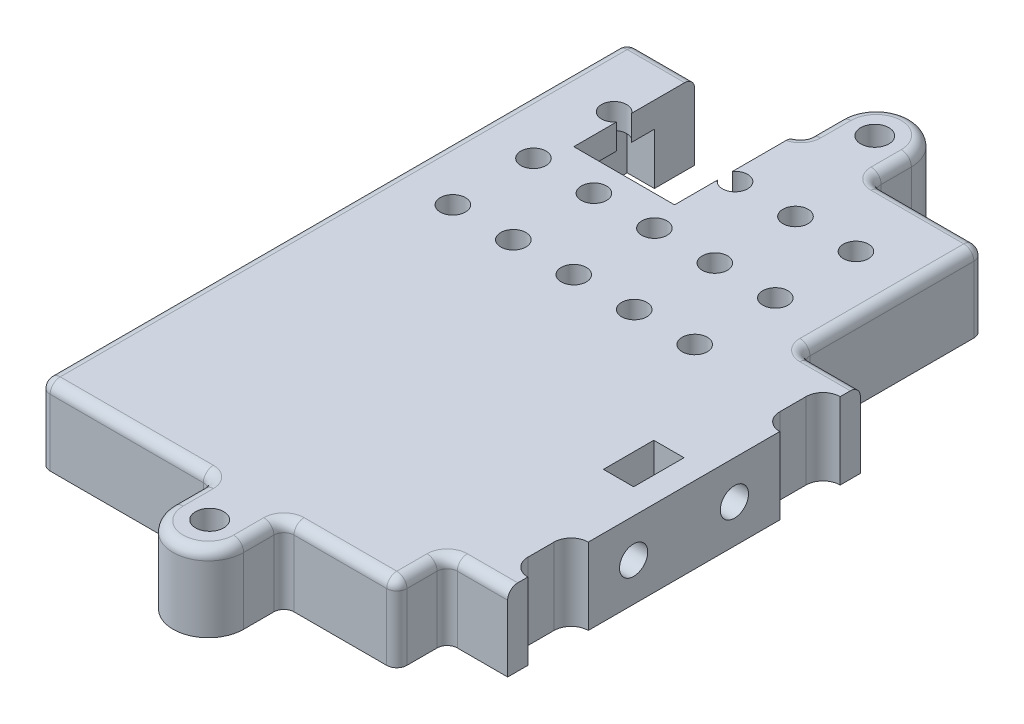
SolidWorks part; units mm, degrees
ref_plane "Front Plane" through (0, 0, 0) normal (0, 0, 1) x (1, 0, 0)
ref_plane "Top Plane" through (0, 0, 0) normal (0, 1, 0) x (1, 0, 0)
ref_plane "Right Plane" through (0, 0, 0) normal (1, 0, 0) x (0, 0, -1)
sketch "Sketch1" plane through (0, 0, 0) normal (0, 1, 0) x (1, 0, 0)
  line L0 (-12.7, -24.13) -> (12.7, -24.13) construction
  line L1 (-12.7, -24.13) -> (-12.7, 24.13) construction
  line L2 (-12.7, 24.13) -> (12.7, 24.13) construction
  line L3 (12.7, -24.13) -> (12.7, 24.13) construction
  line L4 (0, 24.13) -> (0, -24.13) construction
  line L6 (-13.7, 25.13) -> (13.7, 25.13)
  line L7 (-13.7, 25.13) -> (-13.7, -25.13)
  line L8 (-13.7, -25.13) -> (13.7, -25.13)
  line L9 (13.7, 25.13) -> (13.7, -25.13)
  line L10 (-17.7, 29.13) -> (17.7, 29.13)
  line L11 (-17.7, 29.13) -> (-17.7, -29.13)
  line L12 (-17.7, -29.13) -> (17.7, -29.13)
  line L13 (17.7, 29.13) -> (17.7, -29.13)
  point P6 (0, 0)
  point P16 (0, 29.13)
  point P17 (-13.7, 0)
  point P18 (-17.7, 0)
  dimension "D1" = 48.26
  dimension "D2" = 25.4
  dimension "D3" = 1
  dimension "D4" = 1
  dimension "D5" = 1
  dimension "D6" = 1
  dimension "D7" = 4
  dimension "D8" = 4
extrude "Base" add sketch "Sketch1" along normal blind 5.1
sketch "Sketch2" plane through (0, 5.1, 0) normal (0, 1, 0) x (1, 0, 0)
  line L0 (0, 29.13) -> (0, -29.13) construction
  line L1 (-17.7, 29.13) -> (17.7, 29.13)
  line L2 (-17.7, 29.13) -> (-17.7, -29.13)
  line L3 (-17.7, -29.13) -> (17.7, -29.13)
  line L4 (17.7, 29.13) -> (17.7, -29.13)
  circle A0 centre (-12, 22.13) radius 1.25
  circle A1 centre (-6, 22.13) radius 1.25
  circle A2 centre (0, 22.13) radius 1.25
  circle A3 centre (6, 22.13) radius 1.25
  circle A4 centre (12, 22.13) radius 1.25
  circle A5 centre (-6, 14.13) radius 1.25
  circle A6 centre (0, 14.13) radius 1.25
  circle A7 centre (6, 14.13) radius 1.25
  circle A8 centre (12, 14.13) radius 1.25
  circle A9 centre (-6, 6.13) radius 1.25
  circle A10 centre (0, 6.13) radius 1.25
  circle A11 centre (6, 6.13) radius 1.25
  circle A12 centre (12, 6.13) radius 1.25
  circle A13 centre (-12, 14.13) radius 1.25
  circle A14 centre (-12, 6.13) radius 1.25
  point P10 (0, 0)
  dimension "D1" = 2.5
  dimension "D2" = 12
  dimension "D3" = 7
  dimension "D6" = 6
  dimension "D7" = 8
  dimension "D4" = 5
  dimension "D5" = 3
extrude "Top Cover" add sketch "Sketch2" along normal blind 2.5
sketch "Sketch3" plane through (0, 0, 0) normal (0, 1, 0) x (1, 0, 0)
  line L0 (-0.5, 29.13) -> (6.5, 29.13)
  line L1 (17.7, 29.13) -> (-17.7, 29.13) construction
  line L2 (-17.7, 0) -> (17.7, 0) construction
  line L3 (-17.7, 29.13) -> (-17.7, -29.13) construction
  line L4 (17.7, -29.13) -> (17.7, 29.13) construction
  line L5 (-0.5, 29.13) -> (-0.5, 33.13)
  line L6 (6.5, 29.13) -> (6.5, 33.13)
  line L7 (-0.5, -29.13) -> (-0.5, -33.13)
  line L8 (-0.5, -29.13) -> (6.5, -29.13)
  line L9 (6.5, -29.13) -> (6.5, -33.13)
  circle A0 centre (3, 33) radius 1.4
  arc A1 (-0.5, 33.13) -> (6.5, 33.13) centre (3, 33.13) cw
  circle A2 centre (3, -33) radius 1.4
  arc A3 (-0.5, -33.13) -> (6.5, -33.13) centre (3, -33.13) ccw
  point P10 (3, 29.13)
  point P24 (0, 0)
  dimension "D2" = 33
  dimension "D3" = 2.8
  dimension "D4" = 4
  dimension "D1" = 7
  dimension "D5" = 3
extrude "Mounting Ends" add sketch "Sketch3" along normal up to surface (7.6 mm away) up to face at (-12, 7.6, -12.88)
sketch "Sketch5" plane through (0, 0, 0) normal (0, 1, 0) x (1, 0, 0)
  line L0 (17.7, -24.13) -> (23.7, -24.13)
  line L1 (17.7, -29.13) -> (17.7, 29.13) construction
  line L3 (23.7, 10.87) -> (17.7, 10.87)
  line L4 (6.5, -29.13) -> (17.7, -29.13) construction
  line L5 (23.7, -24.13) -> (23.7, -22.13)
  line L6 (23.7, -16.13) -> (23.7, 2.87)
  line L7 (22, -17.83) -> (22, -20.43)
  line L8 (23.7, 10.87) -> (23.7, 8.87)
  line L9 (22, 4.57) -> (22, 7.17)
  line L10 (17.7, 10.87) -> (17.7, -24.13)
  arc A0 (22, -20.43) -> (23.7, -22.13) centre (23.7, -20.43) ccw
  arc A1 (22, -17.83) -> (23.7, -16.13) centre (23.7, -17.83) cw
  arc A2 (22, 4.57) -> (23.7, 2.87) centre (23.7, 4.57) ccw
  arc A3 (22, 7.17) -> (23.7, 8.87) centre (23.7, 7.17) cw
  point P20 (23.7, -22.13)
  point P21 (22, 5.87)
  point P22 (22, -19.13)
  point P23 (22, -20.43)
  point P24 (22, -17.83)
  point P25 (0, 0)
  point P26 (23.7, -17.83)
  point P27 (22, -20.43)
  point P28 (0, 0)
  point P29 (23.7, 4.57)
  point P30 (22, 4.57)
  point P31 (0, 0)
  dimension "D4" = 1.7
  dimension "D1" = 6
  dimension "D2" = 5
  dimension "D3" = 35
  dimension "D5" = 6
  dimension "D6" = 2.6
  dimension "D7" = 2.6
  dimension "D8" = 25
  dimension "D9" = 2
extrude "Basket Mounting Edge" add sketch "Sketch5" along normal up to surface (7.6 mm away) up to face at (-12, 7.6, -12.88)
sketch "Sketch6" plane through (23.7, 0, 0) normal (1, 0, 0) x (0, 0, -1)
  line L0 (-16.13, 3.8) -> (2.87, 3.8) construction
  line L1 (-16.13, 7.6) -> (-16.13, 0) construction
  line L2 (2.87, 7.6) -> (2.87, 0) construction
  line L3 (-6.63, 7.6) -> (-6.63, 0) construction
  line L4 (-16.13, 7.6) -> (2.87, 7.6) construction
  line L5 (-16.13, 0) -> (2.87, 0) construction
  circle A0 centre (-11.63, 3.8) radius 1.4
  circle A1 centre (-1.63, 3.8) radius 1.4
  dimension "D1" = 2.8
  dimension "D2" = 4.5
extrude "Basket Clamp Screw Holes" cut sketch "Sketch6" against normal blind 8
fillet "1mm Edge Fillets" radius 1 22 edges at (-9.1, 7.6, -29.13) (12.1, 7.6, 29.13) (-0.5, 7.6, -31.13) (6.5, 7.6, 31.13) (3, 7.6, -36.63) (3, 7.6, 36.63) (6.5, 7.6, -31.13) (-0.5, 7.6, 31.13) (17.7, 7.6, -20) (-17.7, 7.6, 0) (-17.7, 3.8, 29.13) (-0.5, 3.8, 29.13) (6.5, 3.8, 29.13) (17.7, 3.8, 29.13) (17.7, 3.8, -29.13) (6.5, 3.8, -29.13) (-0.5, 3.8, -29.13) (-17.7, 3.8, -29.13) (20.7, 7.6, -10.87) (20.7, 7.6, 24.13) (17.7, 3.8, -10.87) (17.7, 3.8, 24.13)
sketch "Sketch4" plane through (0, 7.6, 0) normal (0, 1, 0) x (1, 0, 0)
  line L0 (-16.7, 29.13) -> (-1.5, 29.13) construction
  line L1 (-11, 29.13) -> (-1, 29.13)
  line L2 (-11, 29.13) -> (-11, 17.13)
  line L3 (-11, 17.13) -> (-1, 17.13)
  line L4 (-1, 29.13) -> (-1, 17.13)
  line L5 (0, 0) -> (0, 28.8071) construction
  arc A0 (-1.5, 28.13) -> (0.5, 30.13) centre (-1.5, 30.13) ccw construction
  point P9 (0, 0)
  dimension "D1" = 1
  dimension "D2" = 10
  dimension "D3" = 12
extrude "Antenna Clip Hole" cut sketch "Sketch4" against normal through all
sketch "Sketch7" plane through (0, 7.6, 0) normal (0, 1, 0) x (1, 0, 0)
  line L0 (23.7, -16.13) -> (23.7, 2.87) construction
  line L1 (18.2, -4.13) -> (21.2, -4.13)
  line L2 (18.2, -4.13) -> (18.2, -9.13)
  line L3 (18.2, -9.13) -> (21.2, -9.13)
  line L4 (21.2, -4.13) -> (21.2, -9.13)
  point P6 (23.7, -6.63)
  point P7 (21.2, -6.63)
  dimension "D1" = 2.5
  dimension "D2" = 3
  dimension "D3" = 5
extrude "Zip Tie Hole" cut sketch "Sketch7" against normal through all
